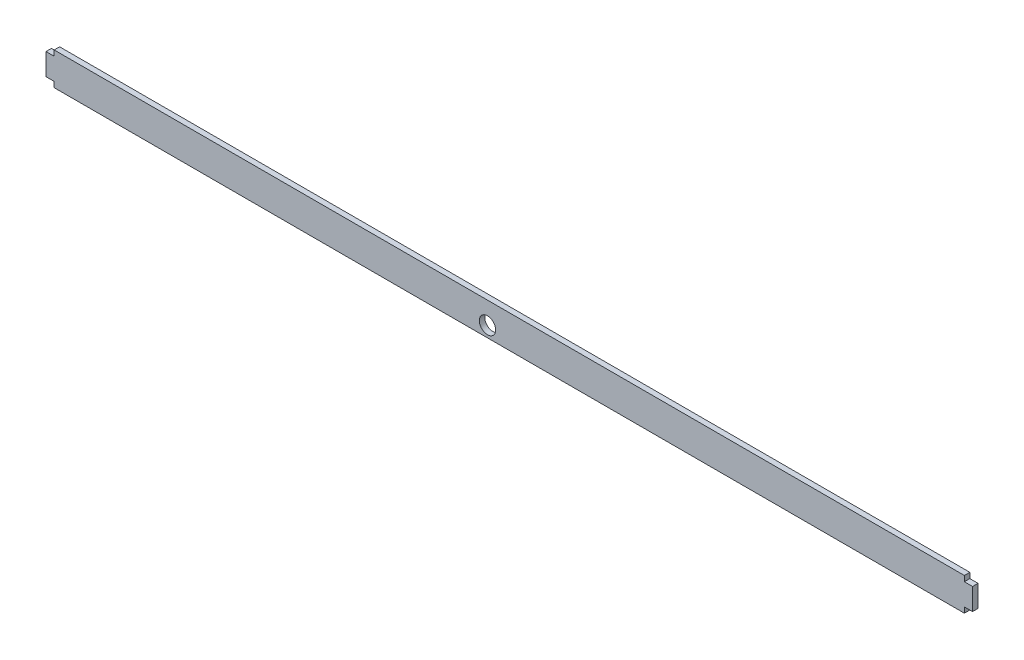
SolidWorks part; units mm, degrees
ref_plane "Front Plane" through (0, 0, 0) normal (0, 0, 1) x (1, 0, 0)
ref_plane "Top Plane" through (0, 0, 0) normal (0, 1, 0) x (1, 0, 0)
ref_plane "Right Plane" through (0, 0, 0) normal (1, 0, 0) x (0, 0, -1)
sketch "Sketch1" plane through (0, 0, 0) normal (0, 0, 1) x (1, 0, 0)
  line L0 (530.225, 15.875) -> (530.225, 19.05)
  line L1 (0, 0) -> (530.225, 0)
  line L2 (0, 0) -> (0, 3.175)
  line L3 (0, 19.05) -> (530.225, 19.05)
  line L4 (530.225, 0) -> (530.225, 3.175)
  line L5 (0, 3.175) -> (-4.7625, 3.175)
  line L7 (0, 15.875) -> (-4.7625, 15.875)
  line L8 (-4.7625, 3.175) -> (-4.7625, 15.875)
  line L13 (530.225, 3.175) -> (534.9875, 3.175)
  line L15 (530.225, 15.875) -> (534.9875, 15.875)
  line L16 (534.9875, 3.175) -> (534.9875, 15.875)
  line L17 (0, 15.875) -> (0, 19.05)
  point P10 (0, 0)
  point P12 (0, 24.349)
  point P17 (0, 25.143)
  point P18 (0, 0)
  dimension "D1" = 19.05
  dimension "D2" = 530.225
  dimension "D3" = 12.7
  dimension "D4" = 3.175
  dimension "D5" = 4.7625
  dimension "D6" = 12.7
  dimension "D7" = 4.7625
  dimension "D8" = 3.175
extrude "Boss-Extrude1" add sketch "Sketch1" along normal blind 3.175
sketch "Sketch2" plane through (0, 0, 3.175) normal (0, 0, 1) x (1, 0, 0)
  line L6 (-4.7625, 15.875) -> (-4.7625, 3.175) construction
  line L7 (0, 0) -> (530.225, 0) construction
  circle A1 centre (252.4125, 6.35) radius 4.7625
  circle A2 centre (252.4125, 6.35) radius 6.35 construction
  dimension "D1" = 257.175
  dimension "D2" = 9.525
  dimension "D3" = 12.7
extrude "Cut-Extrude1" cut sketch "Sketch2" against normal through all
